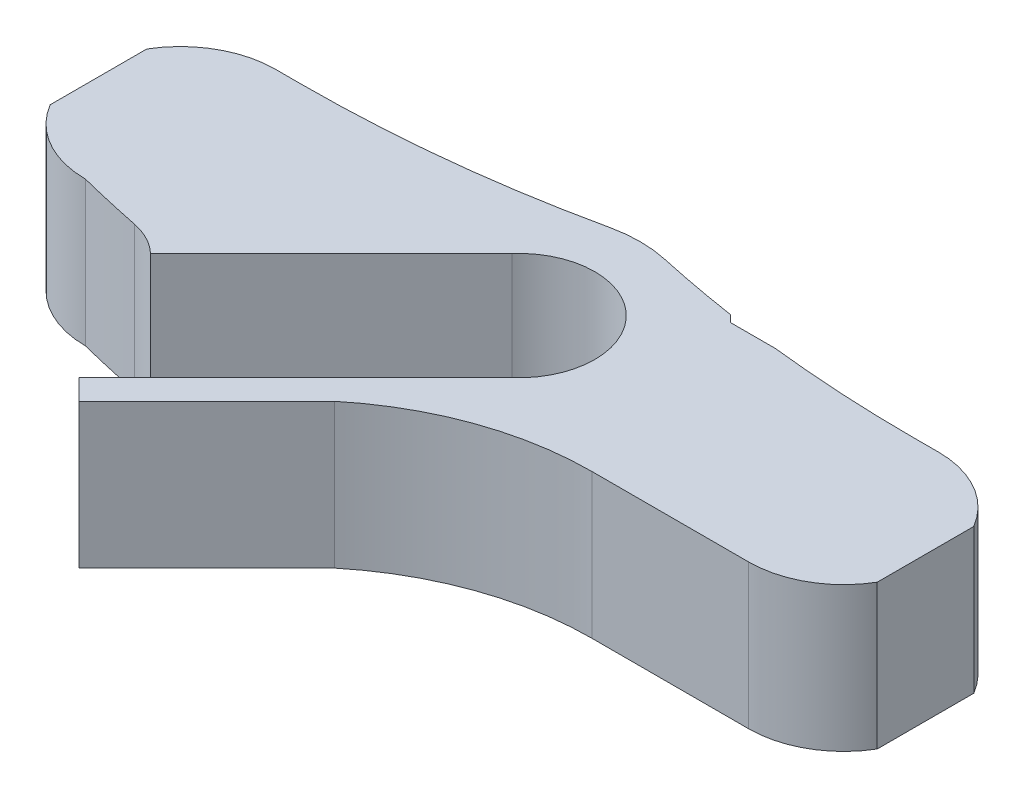
SolidWorks part; units mm, degrees
ref_plane "Front Plane" through (0, 0, 0) normal (0, 0, 1) x (1, 0, 0)
ref_plane "Top Plane" through (0, 0, 0) normal (0, 1, 0) x (1, 0, 0)
ref_plane "Right Plane" through (0, 0, 0) normal (1, 0, 0) x (0, 0, -1)
sketch "Sketch1" plane through (0, 0, 0) normal (0, 1, 0) x (1, 0, 0)
  line L0 (0, 0) -> (74.35, 0)
  line L1 (0, 0) -> (9.45, 0)
  line L2 (37.175, 0) -> (37.175, 19.4169) construction
  line L3 (7.4, 0) -> (11.5, 0) construction
  line L4 (11.5, 0) -> (55.6, 0)
  line L5 (3.5, 7.5) -> (3.5, -7.5)
  line L6 (3.5, 7.5) -> (63.6, 7.5)
  line L7 (3.5, -7.5) -> (63.6, -7.5)
  line L8 (63.6, 7.5) -> (63.6, -7.5)
  line L9 (3.5, 7.5) -> (63.6, -7.5) construction
  line L10 (3.5, -7.5) -> (63.6, 7.5) construction
  line L11 (33.55, 0) -> (33.55, 20.486) construction
  line L12 (9.45, 0) -> (57.65, 0) construction
  line L13 (41.4873, 7.9373) -> (37.7043, 4.1543) construction
  line L14 (37.5805, 11.844) -> (45.394, 4.0305)
  line L15 (37.5805, 11.844) -> (21.706, -4.0305)
  line L16 (21.706, -4.0305) -> (29.5195, -11.844)
  line L17 (45.394, 4.0305) -> (29.5195, -11.844)
  line L18 (37.5805, 11.844) -> (29.5195, -11.844) construction
  line L19 (21.706, -4.0305) -> (45.394, 4.0305) construction
  line L20 (3.5, -7.5) -> (63.6, -7.5)
  line L21 (3.5, -7.5) -> (3.5, -11.844)
  line L22 (63.6, -7.5) -> (63.6, -11.844)
  line L23 (3.5, -11.844) -> (63.6, -11.844)
  line L24 (21.706, -4.0305) -> (13.8924, -11.844)
  line L25 (57.65, 3.9068) -> (57.65, -3.9068) construction
  line L26 (63.6, -3.9068) -> (37.4568, -3.9068) construction
  line L27 (63.6, 3.8467) -> (45.394, 4.0305) construction
  line L28 (57.65, -4.9068) -> (46.2676, -4.9068) construction
  line L29 (45.394, 4.0305) -> (3.5, 4.0305) construction
  line L30 (37.4568, -3.9068) -> (3.5, -3.9068) construction
  line L31 (57.65, 4.9068) -> (55.7709, 4.9068) construction
  line L32 (33.5666, 7.4961) -> (33.55, 7.5)
  line L33 (33.5334, 7.4961) -> (33.55, 7.5)
  line L34 (9.45, 4.9068) -> (11.3291, 4.9068) construction
  line L35 (9.45, 6.9068) -> (11.3291, 6.9068)
  line L36 (57.65, 6.9068) -> (55.7709, 6.9068)
  line L37 (57.65, -6.9068) -> (46.2676, -6.9068)
  line L38 (20.2917, -4.0305) -> (29.5195, -13.2583) construction
  line L39 (46.8083, 4.0305) -> (29.5195, -13.2583) construction
  line L40 (37.5805, 13.2583) -> (46.8083, 4.0305) construction
  line L41 (37.5805, 13.2583) -> (20.2917, -4.0305)
  line L42 (33.55, 0) -> (21.8297, -11.7203) construction
  line L43 (9.45, -3.9068) -> (20.4155, -3.9068)
  line L44 (32.4923, -11.844) -> (27.6783, -16.6581)
  line L45 (20.2917, -4.0305) -> (18.4155, -5.9068) construction
  line L46 (37.7043, 4.1543) -> (21.8297, -11.7203) construction
  line L47 (21.706, -4.0305) -> (29.5195, -11.844)
  line L48 (21.706, -4.0305) -> (17.9229, -7.8135)
  line L49 (29.5195, -11.844) -> (25.7365, -15.6271)
  line L50 (17.9229, -7.8135) -> (25.7365, -15.6271)
  line L51 (18.4155, -5.9068) -> (16.5087, -7.8135)
  line L52 (25.7365, -15.6271) -> (26.6989, -16.5895)
  line L53 (29.5195, -11.844) -> (32.4923, -11.844)
  line L54 (25.7365, -15.6271) -> (27.2229, -17.1135)
  line L55 (25.7365, -15.6271) -> (31.0059, -10.3576)
  line L56 (27.2229, -17.1135) -> (32.4923, -11.844)
  line L57 (31.0059, -10.3576) -> (32.4923, -11.844)
  circle A0 centre (9.45, 0) radius 2.05 construction
  circle A1 centre (57.65, 0) radius 2.05 construction
  arc A2 (29.6432, 3.9068) -> (37.4568, -3.9068) centre (33.7901, 0.2401) cw
  arc A3 (57.65, -3.9068) -> (57.65, 3.9068) centre (57.65, 0) ccw construction
  arc A4 (57.65, -4.9068) -> (57.65, 4.9068) centre (57.65, 0) ccw construction
  arc A5 (46.2676, -4.9068) -> (29.5195, -11.844) centre (46.2676, -28.5921) ccw construction
  arc A6 (9.45, -3.9068) -> (9.45, 3.9068) centre (9.45, 0) cw
  arc A7 (9.45, -4.9068) -> (9.45, 4.9068) centre (9.45, 0) cw construction
  arc A8 (35.1153, 7.1433) -> (55.7709, 4.9068) centre (55.7709, 101.4068) ccw construction
  arc A9 (11.3291, 4.9068) -> (31.9847, 7.1433) centre (11.3291, 101.4068) ccw construction
  arc A11 (9.45, -6.9068) -> (9.45, 6.9068) centre (9.45, 0) cw
  arc A12 (35.1153, 7.1433) -> (31.9847, 7.1433) centre (33.55, 0) ccw construction
  arc A13 (11.3291, 6.9068) -> (31.5566, 9.097) centre (11.3291, 101.4068) ccw
  arc A14 (35.5434, 9.097) -> (31.5566, 9.097) centre (33.55, 0) ccw
  arc A15 (35.5434, 9.097) -> (55.7709, 6.9068) centre (55.7709, 101.4068) ccw
  arc A16 (57.65, -6.9068) -> (57.65, 6.9068) centre (57.65, 0) ccw
  arc A17 (46.2676, -6.9068) -> (32.4923, -11.844) centre (46.2676, -28.5921) ccw
  arc A18 (46.2676, -6.9068) -> (30.9337, -13.2583) centre (46.2676, -28.5921) ccw construction
  arc A19 (9.45, -6.9068) -> (17.9229, -7.8135) centre (13.1046, -12.7975) cw
  arc A20 (20.4155, -3.9068) -> (21.706, -4.0305) centre (21.0097, -4.501) cw
  point P12 (3.5, 0)
  point P19 (33.55, 0)
  point P29 (37.7043, 4.1543)
  point P36 (57.65, 0)
  point P58 (44.5178, 4.9068)
  point P61 (22.5822, 4.9068)
  dimension "D3" = 4.1
  dimension "D5" = 4.1
  dimension "D6" = 0
  dimension "D12" = 22.45
  dimension "D14" = 7.8135
  dimension "D15" = 1
  dimension "D16" = 0
  dimension "D17" = 96.5
  dimension "D18" = 96.5
  dimension "D19" = 7.3128
  dimension "D20" = 2
  dimension "D21" = 1
  dimension "D22" = 16.575
  dimension "D23" = 45
  dimension "D24" = 0
  dimension "D25" = 14.2473
  dimension "D1" = 74.35
  dimension "D2" = 7.4
  dimension "D4" = 55.6
  dimension "D7" = 3.5
  dimension "D8" = 15
  dimension "D9" = 63.6
  dimension "D10" = 5.35
  dimension "D11" = 11.05
  dimension "D13" = 45
  dimension "D26" = 22.45
  dimension "D27" = 14.1521
  dimension "D28" = 1
extrude "Boss-Extrude2" add sketch "Sketch1" along normal blind 10.5 contours A17 L37 A16 L0 L17 A2 L7 | A17 L7 L17 L23 | L41 A20 L15 L4 | A6 L43 L41 L0 | A11 L43 A6 L0 | A13 L35 A11 L0 L41 L6 | L15 A2 L6 L41 L4 | L15 A14 L41 L6 | L41 A14 A13 L6 | A15 A14 L15 L6 | A15 L6 L15 A2 L0 L17 L14 | L0 A16 L36 A15 L14 L17 | L0 A2 L17 | L54 L55 L57 L56 region at (16.5098, 0, -3.6995) region at (14.3913, 0, 1.8171) region at (11.2521, 0, 4.5305) region at (28.7789, 0, -3.7498) region at (23.1505, 0, 1.8885) region at (33.4099, 0, -8.3875) region at (29.3676, 0, -8.1382) region at (39.6274, 0, -4.628) region at (39.7703, 0, 0.9628) region at (37.0847, 0, -8.0854) region at (52.9903, 0, -3.3995) region at (49.9395, 0, 3.6348) region at (34.7947, 0, 9.077)
sketch "Sketch3" plane through (0, 10.5, 0) normal (0, 1, 0) x (1, 0, 0)
  line L0 (3.5, 7.5) -> (3.5, -7.5) construction
  line L1 (3.5, 7.5) -> (63.6, 7.5) construction
  line L2 (63.6, 7.5) -> (63.6, -7.5) construction
  line L3 (3.5, -7.5) -> (63.6, -7.5) construction
  line L4 (3.5, -7.5) -> (63.6, -7.5) construction
  line L5 (3.5, -7.5) -> (3.5, -11.844) construction
  line L6 (3.5, -11.844) -> (63.6, -11.844) construction
  line L7 (63.6, -7.5) -> (63.6, -11.844) construction
  line L8 (46.2676, -6.9068) -> (57.65, -6.9068)
  line L9 (57.65, 6.9068) -> (55.7709, 6.9068)
  line L10 (11.3291, 6.9068) -> (9.45, 6.9068)
  line L11 (17.5759, -7.5) -> (18.2365, -7.5)
  line L12 (18.2365, -7.5) -> (29.6432, 3.9068)
  line L13 (37.4568, -3.9068) -> (25.7365, -15.6271)
  line L14 (25.7365, -15.6271) -> (27.2229, -17.1135)
  line L15 (27.2229, -17.1135) -> (32.4923, -11.844)
  line L16 (46.2676, -6.9068) -> (57.65, -6.9068)
  line L17 (57.65, 6.9068) -> (55.7709, 6.9068)
  line L18 (11.3291, 6.9068) -> (9.45, 6.9068)
  line L19 (17.5759, -7.5) -> (18.2365, -7.5)
  line L20 (18.2365, -7.5) -> (29.6432, 3.9068)
  line L21 (37.4568, -3.9068) -> (25.7365, -15.6271)
  line L22 (25.7365, -15.6271) -> (27.2229, -17.1135)
  line L23 (27.2229, -17.1135) -> (32.4923, -11.844)
  line L24 (11.5, 0) -> (55.6, 0) construction
  line L25 (0, 0) -> (74.35, 0) construction
  line L26 (0, 0) -> (9.45, 0) construction
  line L27 (21.706, -4.0305) -> (13.8924, -11.844) construction
  line L28 (21.706, -4.0305) -> (29.5195, -11.844) construction
  line L29 (45.394, 4.0305) -> (29.5195, -11.844) construction
  line L30 (37.5805, 11.844) -> (45.394, 4.0305) construction
  line L31 (37.5805, 11.844) -> (21.706, -4.0305) construction
  line L32 (21.706, -4.0305) -> (29.5195, -11.844) construction
  line L33 (29.5195, -11.844) -> (25.7365, -15.6271) construction
  line L34 (29.5195, -11.844) -> (32.4923, -11.844) construction
  line L35 (21.706, -4.0305) -> (17.9229, -7.8135) construction
  line L36 (9.45, -3.9068) -> (20.4155, -3.9068) construction
  line L37 (33.5666, 7.4961) -> (33.55, 7.5) construction
  line L38 (33.5334, 7.4961) -> (33.55, 7.5) construction
  line L39 (32.4923, -11.844) -> (27.6783, -16.6581) construction
  line L40 (25.7365, -15.6271) -> (27.2229, -17.1135) construction
  line L41 (27.2229, -17.1135) -> (32.4923, -11.844) construction
  line L42 (25.7365, -15.6271) -> (31.0059, -10.3576) construction
  line L43 (31.0059, -10.3576) -> (32.4923, -11.844) construction
  line L44 (57.65, -6.9068) -> (46.2676, -6.9068) construction
  line L45 (57.65, 6.9068) -> (55.7709, 6.9068) construction
  line L46 (9.45, 6.9068) -> (11.3291, 6.9068) construction
  line L47 (37.5805, 13.2583) -> (20.2917, -4.0305) construction
  line L48 (25.7365, -15.6271) -> (26.6989, -16.5895) construction
  line L49 (18.4155, -5.9068) -> (16.5087, -7.8135) construction
  line L50 (17.9229, -7.8135) -> (25.7365, -15.6271) construction
  line L51 (3.5, 7.5) -> (3.5, -7.5)
  line L52 (3.5, 7.5) -> (63.6, 7.5)
  line L53 (63.6, 7.5) -> (63.6, -7.5)
  line L54 (3.5, -7.5) -> (63.6, -7.5)
  line L55 (3.5, -7.5) -> (63.6, -7.5)
  line L56 (3.5, -7.5) -> (3.5, -11.844)
  line L57 (3.5, -11.844) -> (63.6, -11.844)
  line L58 (63.6, -7.5) -> (63.6, -11.844)
  line L59 (11.5, 0) -> (55.6, 0)
  line L60 (0, 0) -> (74.35, 0)
  line L61 (0, 0) -> (9.45, 0)
  line L62 (21.706, -4.0305) -> (13.8924, -11.844)
  line L63 (21.706, -4.0305) -> (29.5195, -11.844)
  line L64 (45.394, 4.0305) -> (29.5195, -11.844)
  line L65 (37.5805, 11.844) -> (45.394, 4.0305)
  line L66 (37.5805, 11.844) -> (21.706, -4.0305)
  line L67 (21.706, -4.0305) -> (29.5195, -11.844)
  line L68 (29.5195, -11.844) -> (25.7365, -15.6271)
  line L69 (29.5195, -11.844) -> (32.4923, -11.844)
  line L70 (21.706, -4.0305) -> (17.9229, -7.8135)
  line L71 (9.45, -3.9068) -> (20.4155, -3.9068)
  line L72 (33.5666, 7.4961) -> (33.55, 7.5)
  line L73 (33.5334, 7.4961) -> (33.55, 7.5)
  line L74 (32.4923, -11.844) -> (27.6783, -16.6581)
  line L75 (25.7365, -15.6271) -> (27.2229, -17.1135)
  line L76 (27.2229, -17.1135) -> (32.4923, -11.844)
  line L77 (25.7365, -15.6271) -> (31.0059, -10.3576)
  line L78 (31.0059, -10.3576) -> (32.4923, -11.844)
  line L79 (57.65, -6.9068) -> (46.2676, -6.9068)
  line L80 (57.65, 6.9068) -> (55.7709, 6.9068)
  line L81 (9.45, 6.9068) -> (11.3291, 6.9068)
  line L82 (37.5805, 13.2583) -> (20.2917, -4.0305)
  line L83 (25.7365, -15.6271) -> (26.6989, -16.5895)
  line L84 (18.4155, -5.9068) -> (16.5087, -7.8135)
  line L85 (17.9229, -7.8135) -> (25.7365, -15.6271)
  line L86 (37.7043, 4.1543) -> (41.611, 0.2475) construction
  line L87 (41.611, 0.2475) -> (33.7975, 8.061) construction
  line L88 (41.611, 0.2475) -> (17.9229, -7.8135) construction
  line L89 (33.7975, 8.061) -> (25.7365, -15.6271) construction
  line L90 (20.5392, -13.0108) -> (38.9947, 5.4447) construction
  line L91 (29.767, -3.783) -> (33.6737, -7.6898) construction
  line L104 (63.6, -3.5073) -> (63.6, 3.5073)
  line L105 (63.6, -3.5073) -> (63.6, 3.5073)
  line L106 (45.1988, 7.5) -> (41.9245, 7.5)
  line L107 (45.1988, 7.5) -> (41.9245, 7.5)
  line L108 (41.9245, 7.5) -> (41.4221, 8.0025)
  line L109 (41.9245, 7.5) -> (41.4221, 8.0025)
  line L110 (3.5, 3.5073) -> (3.5, -3.5073)
  line L111 (3.5, 3.5073) -> (3.5, -3.5073)
  arc A0 (37.4568, -3.9068) -> (29.6432, 3.9068) centre (33.7901, 0.2401) ccw construction
  arc A1 (9.45, 3.9068) -> (9.45, -3.9068) centre (9.45, 0) ccw construction
  arc A2 (21.706, -4.0305) -> (20.4155, -3.9068) centre (21.0097, -4.501) ccw construction
  arc A3 (46.2676, -6.9068) -> (32.4923, -11.844) centre (46.2676, -28.5921) ccw construction
  arc A4 (57.65, -6.9068) -> (57.65, 6.9068) centre (57.65, 0) ccw construction
  arc A5 (35.5434, 9.097) -> (55.7709, 6.9068) centre (55.7709, 101.4068) ccw construction
  arc A6 (35.5434, 9.097) -> (31.5566, 9.097) centre (33.55, 0) ccw construction
  arc A7 (11.3291, 6.9068) -> (31.5566, 9.097) centre (11.3291, 101.4068) ccw construction
  arc A8 (46.2676, -6.9068) -> (32.4923, -11.844) centre (46.2676, -28.5921) ccw
  arc A9 (57.65, -6.9068) -> (63.6, -3.5073) centre (57.65, 0) ccw
  arc A10 (45.1988, 7.5) -> (55.7709, 6.9068) centre (55.7709, 101.4068) ccw
  arc A11 (35.5434, 9.097) -> (31.5566, 9.097) centre (33.55, 0) ccw
  arc A12 (11.3291, 6.9068) -> (31.5566, 9.097) centre (11.3291, 101.4068) ccw
  arc A13 (9.45, 6.9068) -> (3.5, 3.5073) centre (9.45, 0) ccw
  arc A14 (17.5759, -7.5) -> (9.45, -6.9068) centre (13.1046, -12.7975) ccw
  arc A15 (37.4568, -3.9068) -> (29.6432, 3.9068) centre (33.7901, 0.2401) ccw
  arc A16 (46.2676, -6.9068) -> (32.4923, -11.844) centre (46.2676, -28.5921) ccw
  arc A17 (57.65, -6.9068) -> (63.6, -3.5073) centre (57.65, 0) ccw
  arc A18 (45.1988, 7.5) -> (55.7709, 6.9068) centre (55.7709, 101.4068) ccw
  arc A19 (35.5434, 9.097) -> (31.5566, 9.097) centre (33.55, 0) ccw
  arc A20 (11.3291, 6.9068) -> (31.5566, 9.097) centre (11.3291, 101.4068) ccw
  arc A21 (9.45, 6.9068) -> (3.5, 3.5073) centre (9.45, 0) ccw
  arc A22 (17.5759, -7.5) -> (9.45, -6.9068) centre (13.1046, -12.7975) ccw
  arc A23 (37.4568, -3.9068) -> (29.6432, 3.9068) centre (33.7901, 0.2401) ccw
  arc A24 (9.45, 6.9068) -> (9.45, -6.9068) centre (9.45, 0) ccw construction
  arc A25 (17.9229, -7.8135) -> (9.45, -6.9068) centre (13.1046, -12.7975) ccw construction
  arc A26 (37.4568, -3.9068) -> (29.6432, 3.9068) centre (33.7901, 0.2401) ccw
  arc A27 (9.45, 3.9068) -> (9.45, -3.9068) centre (9.45, 0) ccw
  arc A28 (21.706, -4.0305) -> (20.4155, -3.9068) centre (21.0097, -4.501) ccw
  arc A29 (46.2676, -6.9068) -> (32.4923, -11.844) centre (46.2676, -28.5921) ccw
  arc A30 (57.65, -6.9068) -> (57.65, 6.9068) centre (57.65, 0) ccw
  arc A31 (35.5434, 9.097) -> (55.7709, 6.9068) centre (55.7709, 101.4068) ccw
  arc A32 (35.5434, 9.097) -> (31.5566, 9.097) centre (33.55, 0) ccw
  arc A33 (11.3291, 6.9068) -> (31.5566, 9.097) centre (11.3291, 101.4068) ccw
  arc A34 (9.45, 6.9068) -> (9.45, -6.9068) centre (9.45, 0) ccw
  arc A35 (17.9229, -7.8135) -> (9.45, -6.9068) centre (13.1046, -12.7975) ccw
  arc A47 (63.6, 3.5073) -> (57.65, 6.9068) centre (57.65, 0) ccw
  arc A48 (63.6, 3.5073) -> (57.65, 6.9068) centre (57.65, 0) ccw
  arc A49 (35.5434, 9.097) -> (41.4221, 8.0025) centre (55.7709, 101.4068) ccw
  arc A50 (35.5434, 9.097) -> (41.4221, 8.0025) centre (55.7709, 101.4068) ccw
  arc A51 (3.5, -3.5073) -> (9.45, -6.9068) centre (9.45, 0) ccw
  arc A52 (3.5, -3.5073) -> (9.45, -6.9068) centre (9.45, 0) ccw
  dimension "D2" = 13.05
  dimension "D1" = 0
sketch "Sketch4" plane through (0, 0, 0) normal (0, -1, 0) x (1, 0, 0)
  line L0 (20.5392, 13.0108) -> (38.9947, -5.4447) construction
  line L1 (21.706, 4.0305) -> (13.8924, 11.844) construction
  line L2 (20.5392, 13.0108) -> (38.9947, -5.4447)
  line L3 (21.706, 4.0305) -> (13.8924, 11.844)
  line L4 (25.7365, 15.6271) -> (27.2229, 17.1135) construction
  line L5 (25.7365, 15.6271) -> (26.6989, 16.5895) construction
  line L6 (25.7365, 15.6271) -> (27.2229, 17.1135)
  line L7 (25.7365, 15.6271) -> (26.6989, 16.5895)
  line L8 (27.2229, 17.1135) -> (21.8297, 11.7203)
  line L9 (27.2229, 17.1135) -> (23.2068, 21.1296)
  line L10 (21.8297, 11.7203) -> (17.8136, 15.7364)
  line L11 (23.2068, 21.1296) -> (17.8136, 15.7364)
  line L12 (25.7365, 15.6271) -> (20.9085, 20.455)
  line L13 (9.45, 6.9068) -> (10.6402, 8.8252)
  line L14 (16.5328, 9.2514) -> (17.9229, 7.8135)
  line L15 (18.2365, 7.5) -> (17.5759, 7.5)
  arc A0 (9.45, 6.9068) -> (9.45, -6.9068) centre (9.45, 0) ccw construction
  arc A1 (9.1148, 6.8986) -> (9.45, -6.9068) centre (9.45, 0) ccw
  arc A2 (10.5044, 8.6063) -> (16.5328, 9.2514) centre (13.1046, 12.7975) ccw
  arc A3 (9.45, 6.9068) -> (17.9229, 7.8135) centre (13.1046, 12.7975) ccw construction
  arc A4 (9.45, 6.9068) -> (17.9229, 7.8135) centre (13.1046, 12.7975) ccw
  point P12 (16.5328, 9.2514)
  line M8 (27.2229, 17.1135) -> (25.7365, 15.6271)
  line M12 (18.2365, 7.5) -> (17.5759, 7.5)
  arc M13 (17.5759, 7.5) -> (9.45, 6.9068) centre (13.1046, 12.7975) cw
  dimension "D1" = 2
  dimension "D2" = 0.0338
extrude "Boss-Extrude3" add sketch "Sketch4" against normal up to surface (10.5 mm away) contours A4 L3 A2 L13 M13 | A4 L3 M12 | L12 L6 L9 L11 M8 region at (24.4716, 0, 18.3783) region at (17.9137, 0, 7.6039) region at (13.6892, 0, 7.2651) up to face at (33.4626, 10.5, 0.232)
fillet "Fillet1" radius 100 1 edges at (10.5044, 5.25, 8.6063)
